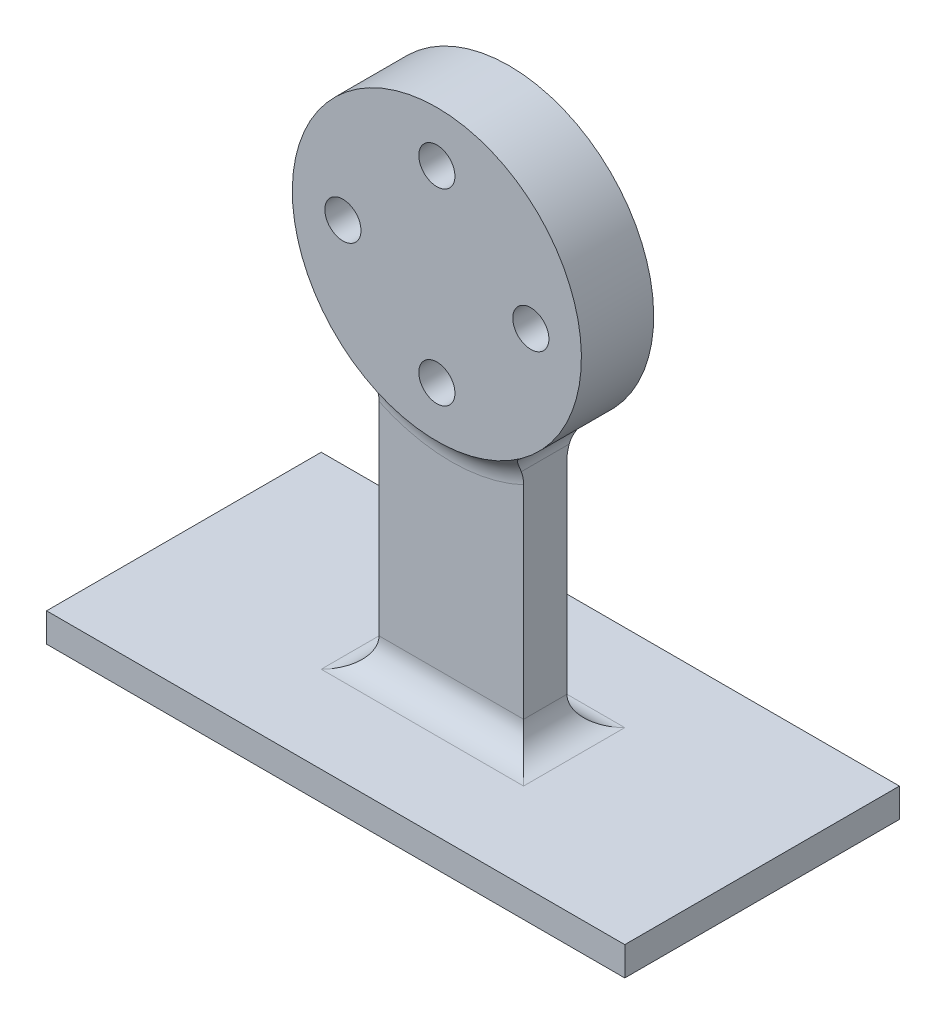
SolidWorks part; units mm, degrees
ref_plane "Front Plane" through (0, 0, 0) normal (0, 0, 1) x (1, 0, 0)
ref_plane "Top Plane" through (0, 0, 0) normal (0, 1, 0) x (1, 0, 0)
ref_plane "Right Plane" through (0, 0, 0) normal (1, 0, 0) x (0, 0, -1)
sketch "Sketch1" plane through (0, 0, 0) normal (0, 0, 1) x (1, 0, 0)
  circle A0 centre (0, 0) radius 10
  dimension "D1" = 20
extrude "Boss-Extrude1" add sketch "Sketch1" along normal blind 5
sketch "Sketch2" plane through (0, 0, 5) normal (0, 0, 1) x (1, 0, 0)
  circle A0 centre (0, 0) radius 6.5 construction
  circle A1 centre (0, 6.5) radius 1.25
  circle A2 centre (6.5, 0) radius 1.25
  circle A3 centre (0, -6.5) radius 1.25
  circle A4 centre (-6.5, 0) radius 1.25
  point P14 (0, 0)
  dimension "D1" = 13
  dimension "D2" = 2.5
  dimension "D3" = 4
extrude "Cut-Extrude1" cut sketch "Sketch2" against normal through all
sketch "Sketch3" plane through (0, 0, 0) normal (0, 0, -1) x (-1, 0, 0)
  circle A0 centre (0, 0) radius 2.5
  dimension "D1" = 5
extrude "Cut-Extrude2" cut sketch "Sketch3" against normal blind 2
ref_plane "Plane1" through (0, 0, 2.5) normal (0, 0, 1) x (1, 0, 0)
sketch "草图2" plane through (0, 0, 2.5) normal (0, 0, 1) x (1, 0, 0)
  line L0 (-5, -8.6603) -> (-5, -26.6603)
  line L1 (-5, -26.6603) -> (5, -26.6603)
  line L2 (5, -26.6603) -> (5, -8.6603)
  line L3 (0, -26.6603) -> (0, -24.4303) construction
  circle A0 centre (0, 0) radius 10 construction
  arc A1 (-5, -8.6603) -> (5, -8.6603) centre (0, 0) ccw
  dimension "D1" = 18
  dimension "D2" = 10
extrude "凸台-拉伸1" add sketch "草图2" along normal blind 1.5 and the other way blind 1.5
sketch "草图3" plane through (0, -26.6603, 0) normal (0, -1, 0) x (1, 0, 0)
  line L0 (0, 4) -> (0, 1) construction
  line L1 (-5, 4) -> (5, 4) construction
  line L2 (-5, 1) -> (5, 1) construction
  line L3 (5, 1) -> (5, 4) construction
  line L4 (-20, 12) -> (20, 12)
  line L5 (-20, 12) -> (-20, -7)
  line L6 (-20, -7) -> (20, -7)
  line L7 (20, 12) -> (20, -7)
  line L8 (-20, 12) -> (20, -7) construction
  line L9 (-20, -7) -> (20, 12) construction
  line L11 (5, 4) -> (-5, 4) construction
  point P6 (0, 2.5)
  point P7 (0, 2.5)
  dimension "D1" = 15
  dimension "D2" = 8
extrude "凸台-拉伸2" add sketch "草图3" along normal blind 2
fillet "圆角1" radius 2 8 edges at (-5, -26.6603, 2.5) (0, -26.6603, 1) (0, -26.6603, 4) (5, -26.6603, 2.5) (5, -8.6603, 2.5) (0, -10, 1) (-5, -8.6603, 2.5) (0, -10, 4)
